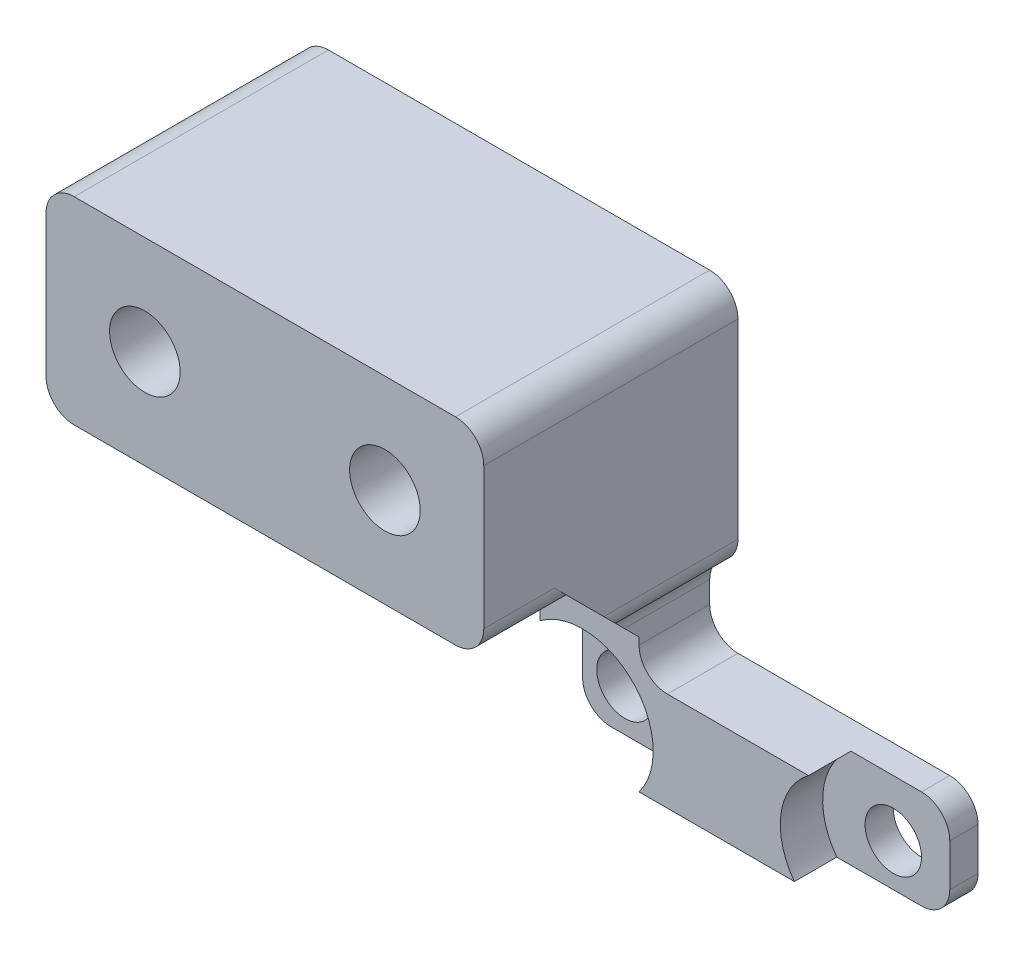
SolidWorks part; units mm, degrees
ref_plane "Plan de face" through (0, 0, 0) normal (0, 0, 1) x (1, 0, 0)
ref_plane "Plan de dessus" through (0, 0, 0) normal (0, 1, 0) x (1, 0, 0)
ref_plane "Plan de droite" through (0, 0, 0) normal (1, 0, 0) x (0, 0, -1)
sketch "Esquisse1" plane through (0, 0, 0) normal (0, 0, 1) x (1, 0, 0)
  line L0 (23.7388, -1.4849) -> (-2.2612, -1.4849) construction
  line L1 (23.7388, -4.4849) -> (-2.2612, -4.4849)
  line L2 (23.7388, -4.4849) -> (23.7388, 2.5151)
  line L3 (23.7388, 2.5151) -> (-2.2612, 2.5151)
  line L4 (-2.2612, -4.4849) -> (-2.2612, 2.5151)
  line L5 (-2.2612, -4.4849) -> (4.7388, -4.4849)
  line L6 (-2.2612, -4.4849) -> (-2.2612, 23.0151)
  line L7 (-2.2612, 23.0151) -> (4.7388, 23.0151)
  line L8 (4.7388, -4.4849) -> (4.7388, 23.0151)
  circle A0 centre (19.7388, -1.4849) radius 2
  circle A1 centre (0.7388, -1.4849) radius 2
  dimension "D6" = 4
  dimension "D1" = 26
  dimension "D2" = 7
  dimension "D3" = 3
  dimension "D4" = 4
  dimension "D5" = 19
  dimension "D7" = 27.5
  dimension "D8" = 7
extrude "Boss.-Extru.1" add sketch "Esquisse1" along normal blind 5 contours L3 L8 L7 L6 | L0 L8 L3 L6 A1 | L8 L0 A1 L4 L1 | L0 L2 L3 L8 A0 | L2 L0 A0 L8 L1 region at (13.5574, -3.0656, 0) region at (13.7431, 0.6188, 0) region at (1.2388, -4.4088, 0) region at (1.3835, 0.8481, 0) region at (1.2388, 12.7651, 0)
sketch "Esquisse5" plane through (0, 0, 5) normal (0, 0, 1) x (1, 0, 0)
  circle A0 centre (0.7388, -1.4849) radius 5
  circle A1 centre (19.7388, -1.4849) radius 5
  dimension "D1" = 10
  dimension "D2" = 10
extrude "Enlèv. mat.-Extru.4" cut sketch "Esquisse5" against normal blind 3
sketch "Esquisse6" plane through (-2.2612, 0, 0) normal (-1, 0, 0) x (0, 0, 1)
  line L0 (5, 2.5151) -> (5, 23.0151) construction
  line L1 (0, 23.0151) -> (5, 23.0151)
  line L2 (0, 23.0151) -> (0, 13.0151)
  line L3 (0, 13.0151) -> (5, 13.0151)
  line L4 (5, 23.0151) -> (5, 13.0151)
  dimension "D1" = 10
extrude "Boss.-Extru.3" add sketch "Esquisse6" along normal blind 20
sketch "Esquisse7" plane through (0, 0, 5) normal (0, 0, 1) x (1, 0, 0)
  line L0 (4.7388, 2.5151) -> (4.7388, 23.0151) construction
  line L1 (-22.2612, 23.0151) -> (4.7388, 23.0151)
  line L2 (-22.2612, 23.0151) -> (-22.2612, 13.0151)
  line L3 (-22.2612, 13.0151) -> (4.7388, 13.0151)
  line L4 (4.7388, 23.0151) -> (4.7388, 13.0151)
extrude "Boss.-Extru.4" add sketch "Esquisse7" along normal blind 13
sketch "Esquisse8" plane through (0, 0, 18) normal (0, 0, 1) x (1, 0, 0)
  line L0 (-22.2612, 18.0151) -> (4.7388, 18.0151) construction
  line L1 (-22.2612, 23.0151) -> (-22.2612, 13.0151) construction
  line L2 (4.7388, 13.0151) -> (4.7388, 23.0151) construction
  line L3 (-17.2612, 18.0151) -> (-0.2612, 18.0151) construction
  line L4 (-17.2612, 20.5151) -> (-0.2612, 20.5151)
  line L5 (-17.2612, 15.5151) -> (-0.2612, 15.5151)
  line L6 (4.7388, 23.0151) -> (-22.2612, 23.0151) construction
  arc A0 (-17.2612, 20.5151) -> (-17.2612, 15.5151) centre (-17.2612, 18.0151) ccw
  arc A1 (-0.2612, 15.5151) -> (-0.2612, 20.5151) centre (-0.2612, 18.0151) ccw
  point P8 (-8.7612, 18.0151)
  point P13 (-8.7612, 20.5151)
  point P16 (-8.7612, 23.0151)
  dimension "D1" = 17
  dimension "D2" = 5
extrude "Enlèv. mat.-Extru.5" cut sketch "Esquisse8" against normal up to vertex (18 mm away) up to point (4.7388, 23.0151, 0)
sketch "Esquisse10" plane through (0, 0, 0) normal (0, 0, -1) x (-1, 0, 0)
  line L0 (17.2612, 18.0151) -> (0.2612, 18.0151) construction
  line L1 (17.2612, 14.2651) -> (0.2612, 14.2651)
  line L2 (17.2612, 21.7651) -> (0.2612, 21.7651)
  arc A0 (17.2612, 14.2651) -> (17.2612, 21.7651) centre (17.2612, 18.0151) ccw
  arc A1 (0.2612, 21.7651) -> (0.2612, 14.2651) centre (0.2612, 18.0151) ccw
  point P4 (8.7612, 18.0151)
  dimension "D1" = 7.5
extrude "Enlèv. mat.-Extru.6" cut sketch "Esquisse10" against normal blind 8
sketch "Esquisse11" plane through (4.7388, 0, 0) normal (1, 0, 0) x (0, 0, -1)
  line L0 (-18, 23.0151) -> (0, 23.0151)
  line L1 (0, 23.0151) -> (0, 2.5151)
  line L2 (0, 2.5151) -> (-5, 2.5151)
  line L3 (-5, 2.5151) -> (-5, 13.0151)
  line L4 (-5, 13.0151) -> (-18, 13.0151)
  line L5 (-18, 13.0151) -> (-18, 23.0151)
extrude "Boss.-Extru.6" add sketch "Esquisse11" along normal blind 2
sketch "Esquisse12" plane through (-22.2612, 0, 0) normal (-1, 0, 0) x (0, 0, 1)
  line L1 (18, 13.0151) -> (0, 13.0151)
  line L2 (18, 13.0151) -> (18, 23.0151)
  line L3 (18, 23.0151) -> (0, 23.0151)
  line L4 (0, 13.0151) -> (0, 23.0151)
extrude "Boss.-Extru.7" add sketch "Esquisse12" along normal blind 2
sketch "Esquisse13" plane through (0, 23.0151, 0) normal (0, 1, 0) x (1, 0, 0)
  line L1 (-24.2612, -18) -> (6.7388, -18)
  line L2 (-24.2612, -18) -> (-24.2612, 0)
  line L3 (-24.2612, 0) -> (6.7388, 0)
  line L4 (6.7388, -18) -> (6.7388, 0)
extrude "Boss.-Extru.8" add sketch "Esquisse13" along normal blind 2
sketch "Esquisse14" plane through (0, 13.0151, 0) normal (0, -1, 0) x (1, 0, 0)
  line L0 (6.7388, 18) -> (6.7388, 5)
  line L1 (6.7388, 5) -> (-2.2612, 5)
  line L2 (-2.2612, 5) -> (-2.2612, 0)
  line L3 (-2.2612, 0) -> (-24.2612, 0)
  line L4 (-24.2612, 0) -> (-24.2612, 18)
  line L5 (-24.2612, 18) -> (6.7388, 18)
extrude "Boss.-Extru.9" add sketch "Esquisse14" along normal blind 2
fillet "Congé1" radius 2 6 edges at (-2.2612, -4.4849, 1) (23.7388, -4.4849, 1) (23.7388, 2.5151, 2.5) (-24.2612, 11.0151, 9) (-24.2612, 25.0151, 9) (6.7388, 25.0151, 9)
sketch "Esquisse15" plane through (0, 0, 8) normal (0, 0, -1) x (-1, 0, 0)
  line L0 (17.2612, 20.5151) -> (0.2612, 20.5151)
  line L1 (0.2612, 15.5151) -> (17.2612, 15.5151)
  circle A0 centre (0.2612, 18.0151) radius 2.5
  circle A1 centre (17.2612, 18.0151) radius 2.5
  line M6 (17.2612, 15.5151) -> (0.2612, 15.5151)
  line M8 (0.2612, 20.5151) -> (17.2612, 20.5151)
extrude "Boss.-Extru.10" add sketch "Esquisse15" against normal blind 10 contours A1 A0 M8 M6 region at (-8.7612, 18.0151, 8)
sketch "Esquisse16" plane through (0, 0, 0) normal (0, 0, -1) x (-1, 0, 0)
  line L0 (0.2612, 21.7651) -> (17.2612, 21.7651)
  line L1 (17.2612, 14.2651) -> (0.2612, 14.2651)
  circle A0 centre (0.2612, 18.0151) radius 3.75
  circle A1 centre (17.2612, 18.0151) radius 3.75
  line M1 (0.2612, 21.7651) -> (17.2612, 21.7651)
  line M3 (17.2612, 14.2651) -> (0.2612, 14.2651)
extrude "Boss.-Extru.11" add sketch "Esquisse16" against normal blind 8 contours A1 A0 M1 M3 region at (-8.7612, 18.0151, 0)
chamfer "Chanfrein1" distance 6 angle 45 1 edges at (2.2388, 11.0151, 5)
fillet "Congé3" radius 2 1 edges at (6.7388, 11.0151, 14.5)
sketch "Esquisse17" plane through (6.7388, 0, 0) normal (1, 0, 0) x (0, 0, -1)
  line L0 (-13, 13.0151) -> (-5, 5.0151) construction
  line L1 (0, 2.5151) -> (-7.5, 2.5151)
  line L2 (0, 2.5151) -> (0, 7.5151)
  line L3 (0, 7.5151) -> (-7.5, 7.5151)
  line L4 (-7.5, 2.5151) -> (-7.5, 7.5151)
  dimension "D1" = 5
extrude "Enlèv. mat.-Extru.7" cut sketch "Esquisse17" against normal blind 2
fillet "Congé4" radius 2 2 edges at (4.7388, 2.5151, 2.5) (6.7388, 7.5151, 3.75)
fillet "Congé5" radius 2 1 edges at (4.7388, 7.5151, 3.75)
fillet "Congé6" radius 2 1 edges at (-2.2612, 11.0151, 5.5)
